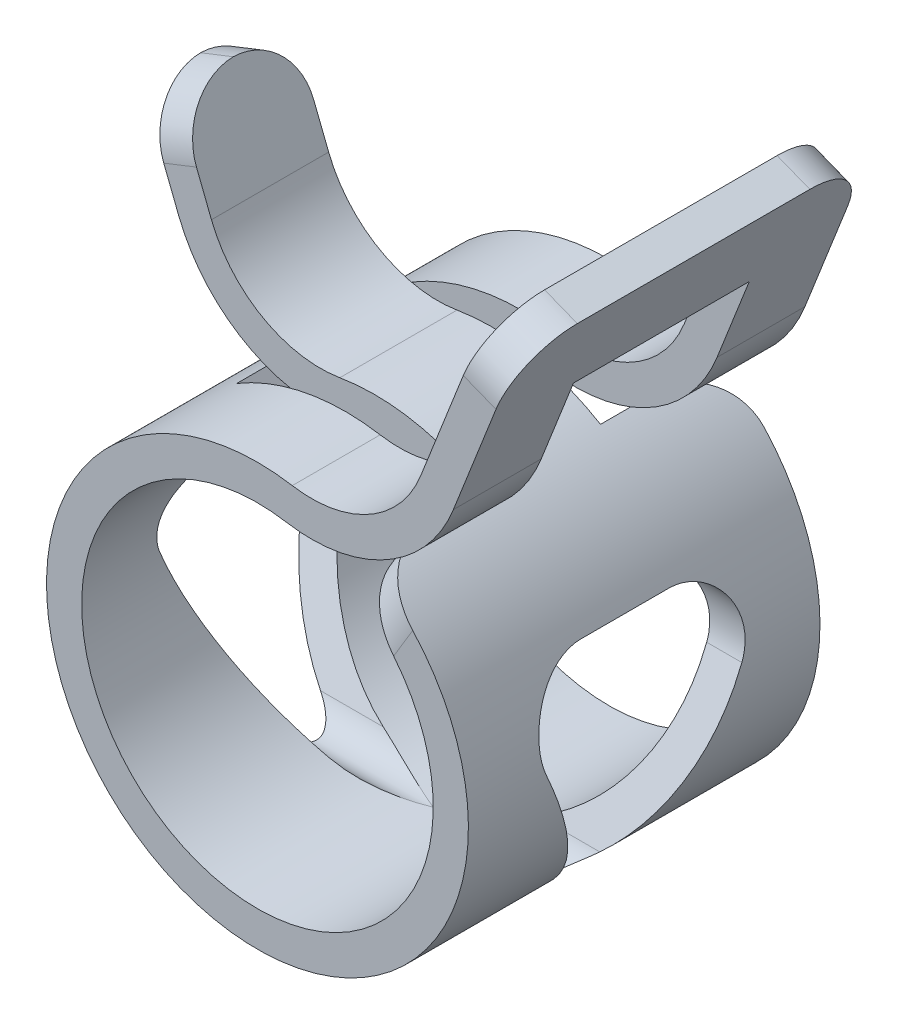
SolidWorks part; units mm, degrees
ref_plane "Front Plane" through (0, 0, 0) normal (0, 0, 1) x (1, 0, 0)
ref_plane "Top Plane" through (0, 0, 0) normal (0, 1, 0) x (1, 0, 0)
ref_plane "Right Plane" through (0, 0, 0) normal (1, 0, 0) x (0, 0, -1)
sketch "Cylinder Sketch" plane through (0, 0, 0) normal (0, 0, 1) x (1, 0, 0)
  circle A0 centre (0, 0) radius 3.6
  circle A1 centre (0, 0) radius 3
  dimension "Inside Diameter" = 6
  dimension "Thickness" = 0.6
extrude "Cylinder Extrude" add sketch "Cylinder Sketch" along normal mid plane 6
sketch "Side Slot Sketch" plane through (0, 0, 0) normal (1, 0, 0) x (0, 0, -1)
  line L0 (-0.75, 1.5) -> (0.75, 1.5)
  line L1 (1.6682, 0.1038) -> (0.4591, -2.6981)
  line L2 (-0.4591, -2.6981) -> (-1.6682, 0.1038)
  line L3 (0, 1.5) -> (0, -3.762) construction
  arc A0 (0.4591, -2.6981) -> (-0.4591, -2.6981) centre (0, -2.5) cw
  arc A1 (0.75, 1.5) -> (1.6682, 0.1038) centre (0.75, 0.5) cw
  arc A2 (-0.75, 1.5) -> (-1.6682, 0.1038) centre (-0.75, 0.5) ccw
  dimension "D1" = 0.5
  dimension "D2" = 1
  dimension "D3" = 1.5
  dimension "Slot Height" = 3
  dimension "D5" = 1.5
extrude "Cut Side Slots" cut sketch "Side Slot Sketch" against normal mid plane 25.4
sketch "Top Slot Sketch" plane through (0, 0, 3) normal (0, 0, 1) x (1, 0, 0)
  line L0 (-2.1631, 3.6) -> (0, 0)
  line L1 (0, 0) -> (2.1631, 3.6)
  line L2 (2.1631, 3.6) -> (-2.1631, 3.6)
  circle A2 centre (0, 0) radius 3.6 construction
  point P0 (0, 3.6)
  dimension "D1" = 62
extrude "Cut Slot in Top" cut sketch "Top Slot Sketch" against normal through all
sketch "Female Base Sketch" plane through (0, 0, 0) normal (0.8572, 0.515, 0) x (0, 0, -1)
  line L0 (-3, 3) -> (3, 3) construction
  line L1 (-3, 3.6) -> (-1.5, 3.6)
  line L2 (-3, 3.6) -> (-3, 3)
  line L3 (-3, 3) -> (-1.5, 3)
  line L4 (-1.5, 3.6) -> (-1.5, 3)
  line L5 (0, 0) -> (3, 0) construction
  line L6 (3, 3.6) -> (1.5, 3.6)
  line L7 (3, 3.6) -> (3, 3)
  line L8 (3, 3) -> (1.5, 3)
  line L9 (1.5, 3.6) -> (1.5, 3)
  line L10 (3, -3) -> (3, 3) construction
  dimension "D1" = 1.5
revolve "Female Base" add sketch "Female Base Sketch" angle 40.5 about L5
sketch "Female Transition Sketch" plane through (0, 0, 0) normal (0.9863, -0.165, 0) x (0, 0, -1)
  line L0 (3, 3) -> (3, 3.6) construction
  line L1 (3, 3.6) -> (1.5, 3.6) construction
  line L2 (1.5, 3.6) -> (1.5, 3) construction
  line L3 (1.5, 3) -> (3, 3) construction
  line L4 (-3, 3.6) -> (-3, 3) construction
  line L5 (-3, 3) -> (-1.5, 3) construction
  line L6 (-1.5, 3) -> (-1.5, 3.6) construction
  line L7 (-1.5, 3.6) -> (-3, 3.6) construction
  line L8 (3, 3) -> (3, 3.6)
  line L9 (3, 3.6) -> (1.5, 3.6)
  line L10 (1.5, 3.6) -> (1.5, 3)
  line L11 (1.5, 3) -> (3, 3)
  line L12 (-3, 3.6) -> (-3, 3)
  line L13 (-3, 3) -> (-1.5, 3)
  line L14 (-1.5, 3) -> (-1.5, 3.6)
  line L15 (-1.5, 3.6) -> (-3, 3.6)
  line L16 (-1.5, 5.6) -> (1.5, 5.6) construction
  dimension "Transition Radius" = 2
revolve "Female Transition Revolve" add sketch "Female Transition Sketch" angle 78 about L16 reverse direction yes
sketch "Female Lever Sketch" plane through (2.0076, 5.0965, 0) normal (0.3665, 0.9304, 0) x (0.9304, -0.3665, 0)
  line L0 (1.4357, 1.5) -> (1.4357, 3) construction
  line L1 (1.4357, 3) -> (0.8357, 3) construction
  line L2 (0.8357, 3) -> (0.8357, 1.5) construction
  line L3 (0.8357, 1.5) -> (1.4357, 1.5) construction
  line L4 (0.8357, -1.5) -> (0.8357, -3) construction
  line L5 (0.8357, -3) -> (1.4357, -3) construction
  line L6 (1.4357, -3) -> (1.4357, -1.5) construction
  line L7 (1.4357, -1.5) -> (0.8357, -1.5) construction
  line L8 (1.4357, 1.5) -> (1.4357, 3)
  line L9 (1.4357, 3) -> (0.8357, 3)
  line L10 (0.8357, 3) -> (0.8357, 1.5)
  line L11 (0.8357, 1.5) -> (1.4357, 1.5)
  line L12 (0.8357, -1.5) -> (0.8357, -3)
  line L13 (0.8357, -3) -> (1.4357, -3)
  line L14 (1.4357, -3) -> (1.4357, -1.5)
  line L15 (1.4357, -1.5) -> (0.8357, -1.5)
extrude "Female Lever Extrude" add sketch "Female Lever Sketch" along normal blind 1.5
sketch "Female Top Sketch" plane through (2.5573, 6.4921, 0) normal (0.3665, 0.9304, 0) x (0.9304, -0.3665, 0)
  line L1 (1.4357, -3) -> (0.8357, -3)
  line L2 (1.4357, -3) -> (1.4357, 3)
  line L3 (1.4357, 3) -> (0.8357, 3)
  line L4 (0.8357, -3) -> (0.8357, 3)
extrude "Female Top Extrude" add sketch "Female Top Sketch" along normal blind 1.5
sketch "Male Base Sketch" plane through (0, 0, 0) normal (-0.8572, 0.515, 0) x (0, 0, 1)
  line L0 (-3, 3.6) -> (3, 3.6) construction
  line L1 (-1, 3.6) -> (1, 3.6)
  line L2 (-1, 3.6) -> (-1, 3)
  line L3 (-1, 3) -> (1, 3)
  line L4 (1, 3.6) -> (1, 3)
  line L5 (-3, 3) -> (3, 3) construction
  line L6 (0, 3) -> (0, 3.6) construction
  line L7 (0, 0) -> (3, 0) construction
  line L9 (3, -3.6) -> (3, 3.6) construction
  dimension "D1" = 2
revolve "Male Base" add sketch "Male Base Sketch" angle 40.5 about L7
sketch "Male Transition Sketch" plane through (0, 0, 0) normal (-0.9863, -0.165, 0) x (0, 0, 1)
  line L0 (-1, 5.6) -> (1, 5.6) construction
  line L4 (-1, 3.6) -> (-1, 3)
  line L5 (-1, 3) -> (1, 3)
  line L6 (1, 3) -> (1, 3.6)
  line L7 (1, 3.6) -> (-1, 3.6)
  line L8 (-1, 3.6) -> (-1, 3)
  line L9 (-1, 3) -> (1, 3)
  line L10 (1, 3) -> (1, 3.6)
  line L11 (1, 3.6) -> (-1, 3.6)
  dimension "D1" = 0
  dimension "Transition Radius" = 2
revolve "Male Transition Revolve" add sketch "Male Transition Sketch" angle 78 about L0 reverse direction yes
sketch "Male Lever Sketch" plane through (-2.0076, 5.0965, 0) normal (-0.3665, 0.9304, 0) x (0.9304, 0.3665, 0)
  line L4 (-0.8357, -1) -> (-0.8357, 1)
  line L5 (-0.8357, 1) -> (-1.4357, 1)
  line L6 (-1.4357, 1) -> (-1.4357, -1)
  line L7 (-1.4357, -1) -> (-0.8357, -1)
  line L8 (-0.8357, -1) -> (-0.8357, 1)
  line L9 (-0.8357, 1) -> (-1.4357, 1)
  line L10 (-1.4357, 1) -> (-1.4357, -1)
  line L11 (-1.4357, -1) -> (-0.8357, -1)
  dimension "D1" = 0
extrude "Male Lever Extrude" add sketch "Male Lever Sketch" along normal blind 1.7143
fillet "Fillets" radius 1.016 6 edges at (1.6996, 2.8287, -3) (1.6996, 2.8287, 3) (-3.6925, 6.2752, 1) (-3.6925, 6.2752, -1) (4.1637, 7.4715, -3) (4.1637, 7.4715, 3)
equation "\"Slot Height@Side Slot Sketch\"=\"Inside Diameter@Cylinder Sketch\"/2"
equation "\"D5@Side Slot Sketch\"=\"Inside Diameter@Cylinder Sketch\"/4"
equation "\"D3@Side Slot Sketch\"=\"Body Width@Cylinder Extrude\"/4"
equation "\"D1@Female Base Sketch\"=\"Body Width@Cylinder Extrude\"/4"
equation "\"D1@Female Top Extrude\"=\"Body Width@Cylinder Extrude\"/4"
equation "\"D1@Male Base Sketch\"=\"Body Width@Cylinder Extrude\"/2-1"
equation "\"D1@Male Lever Extrude\"=\"Body Width@Cylinder Extrude\"/3.5"
equation "\"D1@Female Lever Extrude\"=\"Body Width@Cylinder Extrude\"/4"
